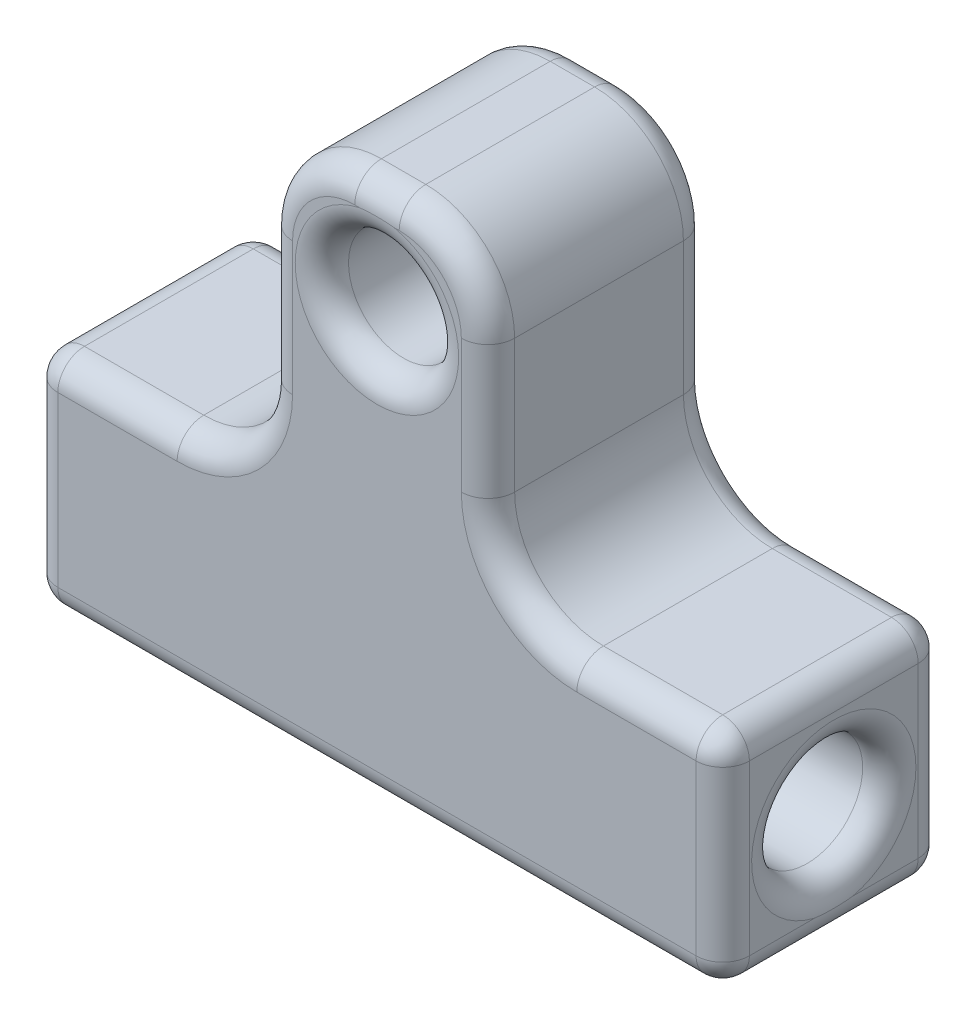
SolidWorks part; units mm, degrees
ref_plane "Front Plane" through (0, 0, 0) normal (0, 0, 1) x (1, 0, 0)
ref_plane "Top Plane" through (0, 0, 0) normal (0, 1, 0) x (1, 0, 0)
ref_plane "Right Plane" through (0, 0, 0) normal (1, 0, 0) x (0, 0, -1)
sketch "Sketch1" plane through (0, 0, 0) normal (0, 0, 1) x (1, 0, 0)
  line L0 (0, 42.6446) -> (0, -51.4876) construction
  line L1 (-40.9091, 0) -> (51.7355, 0) construction
  line L2 (22.5, -5) -> (38.9256, -5)
  line L3 (-2.5, 30) -> (2.5, 30)
  line L4 (-12.5, 20) -> (-12.5, 5)
  line L5 (-12.5, -30) -> (12.5, -30)
  line L6 (12.5, 20) -> (12.5, 5)
  line L7 (-12.5, 30) -> (12.5, -30) construction
  line L8 (-12.5, -30) -> (12.5, 30) construction
  line L9 (-38.9256, -5) -> (-22.5, -5)
  line L10 (-38.9256, -5) -> (-38.9256, -30)
  line L11 (-38.9256, -30) -> (38.9256, -30)
  line L12 (38.9256, -5) -> (38.9256, -30)
  line L13 (-38.9256, -5) -> (38.9256, -30) construction
  line L14 (-38.9256, -30) -> (38.9256, -5) construction
  arc A0 (2.5, 30) -> (12.5, 20) centre (2.5, 20) cw
  arc A1 (-2.5, 30) -> (-12.5, 20) centre (-2.5, 20) ccw
  arc A2 (12.5, 5) -> (22.5, -5) centre (22.5, 5) ccw
  arc A3 (-12.5, 5) -> (-22.5, -5) centre (-22.5, 5) cw
  circle A4 centre (0, 18) radius 6.2
  point P5 (0, 0)
  point P10 (0, -17.5)
  point P25 (12.5, -5)
  dimension "D4" = 10
  dimension "D5" = 12.4
  dimension "D1" = 25
  dimension "D2" = 60
  dimension "D3" = 25
  dimension "D6" = 12
extrude "Boss-Extrude1" add sketch "Sketch1" along normal blind 25 contours A3 L9 L10 L11 L12 L2 A2 L6 A0 L3 A1 L4 | A4
sketch "Sketch2" plane through (38.9256, 0, 0) normal (1, 0, 0) x (0, 0, -1)
  line L0 (-12.5, -5) -> (-12.5, -30) construction
  line L1 (-25, -5) -> (0, -5) construction
  line L2 (-25, -30) -> (0, -30) construction
  circle A0 centre (-12.5, -18) radius 6.25
  dimension "D1" = 12.5
  dimension "D2" = 12
extrude "Cut-Extrude1" cut sketch "Sketch2" against normal through all
fillet "Fillet1" radius 3 32 edges at (-38.9256, -5, 12.5) (-38.9256, -30, 12.5) (-38.9256, -18, 6.25) (6.2, 18, 0) (-15.4289, -2.0711, 0) (-30.7128, -5, 0) (-38.9256, -17.5, 0) (0, -30, 0) (15.4289, -2.0711, 0) (12.5, 12.5, 0) (9.5711, 27.0711, 0) (0, 30, 0) (-9.5711, 27.0711, 0) (-12.5, 12.5, 0) (30.7128, -5, 0) (6.2, 18, 25) (-9.5711, 27.0711, 25) (0, 30, 25) (9.5711, 27.0711, 25) (12.5, 12.5, 25) (15.4289, -2.0711, 25) (30.7128, -5, 25) (0, -30, 25) (-38.9256, -17.5, 25) (-30.7128, -5, 25) (-15.4289, -2.0711, 25) (-12.5, 12.5, 25) (38.9256, -30, 12.5) (38.9256, -17.5, 25) (38.9256, -5, 12.5) (38.9256, -17.5, 0) (38.9256, -18, 6.25)
